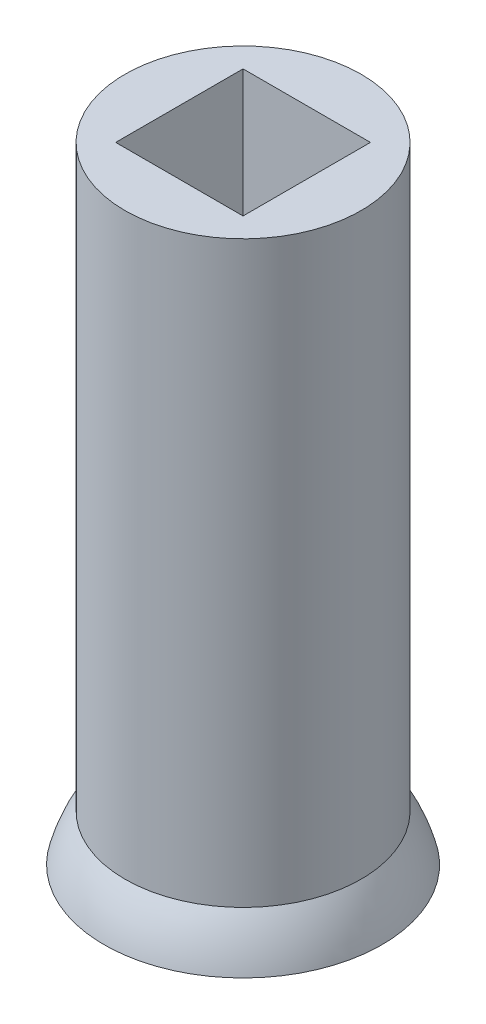
SolidWorks part; units mm, degrees
ref_plane "Front Plane" through (0, 0, 0) normal (0, 0, 1) x (1, 0, 0)
ref_plane "Top Plane" through (0, 0, 0) normal (0, 1, 0) x (1, 0, 0)
ref_plane "Right Plane" through (0, 0, 0) normal (1, 0, 0) x (0, 0, -1)
sketch "Sketch1" plane through (0, 0, 0) normal (0, 1, 0) x (1, 0, 0)
  line L1 (-1.49, 1.99) -> (1.49, 1.99)
  line L2 (-1.49, 1.99) -> (-1.49, -1.99)
  line L3 (-1.49, -1.99) -> (1.49, -1.99)
  line L4 (1.49, 1.99) -> (1.49, -1.99)
  line L5 (-1.49, 1.99) -> (1.49, -1.99) construction
  line L6 (-1.49, -1.99) -> (1.49, 1.99) construction
  circle A0 centre (0, 0) radius 3.49
  point P0 (0, 0)
  dimension "D1" = 2.98
  dimension "D2" = 3.98
  dimension "D3" = 2
extrude "Boss-Extrude2" add sketch "Sketch1" along normal blind 7
sketch "Sketch2" plane through (0, 0, 0) normal (1, 0, 0) x (0, 0, -1)
  line L0 (3.49, 7) -> (-3.49, 7) construction
  line L1 (12, 3) -> (3.49, 3)
  line L2 (3.49, 0) -> (3.49, 7) construction
  line L3 (3.49, 7) -> (10.198, 7)
  line L4 (3.49, 7) -> (3.49, 3)
  line L5 (0, 0.0028) -> (0, 50000.0028) construction
  line L6 (-3.49, 0) -> (3.49, 0) construction
  line L7 (8.544, 6) -> (3.49, 6)
  arc A1 (12, 3) -> (10.198, 7) centre (0, 0) ccw
  arc A2 (10, 3) -> (8.544, 6) centre (0, 0) ccw
  dimension "D2" = 2
  dimension "D1" = 12
  dimension "D3" = 3
  dimension "D4" = 1
ref_axis "Axis1" through (0, -0.35, 0) along (0, 1, 0)
revolve "Revolve1" add sketch "Sketch2" angle 360 about L5 region at (0, 3.094, -11)
sketch "Sketch3" plane through (0, 7, 0) normal (0, 1, 0) x (1, 0, 0)
  line L1 (-5.5, 5.5) -> (5.5, 5.5)
  line L2 (-5.5, 5.5) -> (-5.5, -5.5)
  line L3 (-5.5, -5.5) -> (5.5, -5.5)
  line L4 (5.5, 5.5) -> (5.5, -5.5)
  line L5 (-5.5, 5.5) -> (5.5, -5.5) construction
  line L6 (-5.5, -5.5) -> (5.5, 5.5) construction
  circle A0 centre (0, 0) radius 10.198
  circle A1 centre (0, 0) radius 10.198 construction
  point P0 (0, 0)
  point P11 (1.49, -1.99)
  point P12 (4.1402, -5.7773)
  dimension "D1" = 11
extrude "Boss-Extrude3" add sketch "Sketch3" along normal blind 50
equation "\"pressClearance\"=0.02"
equation "\"D1@Sketch1\"=3-\"pressClearance\""
equation "\"D2@Sketch1\"=4-\"pressClearance\""
